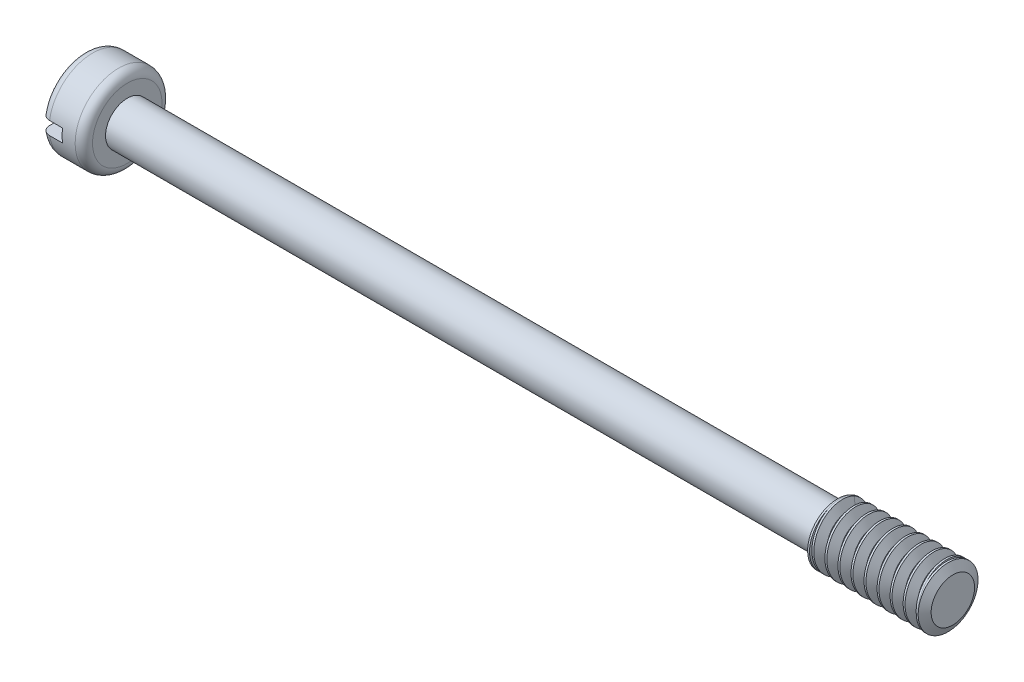
SolidWorks part; units mm, degrees
ref_plane "Front Plane" through (0, 0, 0) normal (0, 0, 1) x (1, 0, 0)
ref_plane "Top Plane" through (0, 0, 0) normal (0, 1, 0) x (1, 0, 0)
ref_plane "Right Plane" through (0, 0, 0) normal (1, 0, 0) x (0, 0, -1)
sketch "Sketch1" plane through (0, 0, 0) normal (0, 0, 1) x (1, 0, 0)
  line L0 (0, 0.8) -> (0, 0)
  line L1 (0, 0) -> (20, 0)
  line L2 (20, 0) -> (20, 0.5)
  line L3 (20, 0.5) -> (1, 0.5)
  line L4 (1, 0.5) -> (1, 0.8)
  line L5 (0.8, 1) -> (0.2, 1)
  arc A0 (1, 0.8) -> (0.8, 1) centre (0.8, 0.8) ccw
  arc A1 (0, 0.8) -> (0.2, 1) centre (0.2, 0.8) cw
  point P9 (1, 1)
  point P12 (0, 1)
  dimension "D5" = 0.2
  dimension "D1" = 20
  dimension "D2" = 0.5
  dimension "D3" = 1
  dimension "D4" = 1
revolve "Revolve2" add sketch "Sketch1" angle 360 about L1
thread "Thread1" pitch 0.35 method extrude profile "Thread Profile1" start angle 0, offset 0, length 2.5, pitch 0.3, diameter 1
ref_plane "Plane1" through (20, 0, 0.5) normal (0, -1, 0) x (0, 0, 1)
sketch "Thread Profile1" plane through (20, 0, 0.5) normal (0, -1, 0) x (0, 0, 1)
  line L0 (0, 0) -> (0, 0.35) construction
  line L1 (0, 0) -> (0.1894, 0.1094)
  line L2 (0.1894, 0.1094) -> (0.1894, 0.1531)
  line L3 (0.1894, 0.1531) -> (0, 0.2625)
  line L4 (0.1894, 0.1312) -> (0, 0.1312) construction
  line L11 (0, 0) -> (0, 0.2625)
  point P2 (0, 0)
  dimension "Pitch" = 0.35
  dimension "Profile_Angle" = 60
  dimension "Profile_Land" = 0.0437
  dimension "Profile_Height" = 0.1894
sketch "Sketch4" plane through (0, 0, 0) normal (0, -1, 0) x (1, 0, 0)
  line L4 (19.8906, 0.6894) -> (19.8469, 0.6894)
  line L5 (19.8469, 0.6894) -> (19.7375, 0.5)
  line L6 (19.7375, 0.5) -> (20, 0.5)
  line L7 (20, 0.5) -> (19.8906, 0.6894)
  line L8 (19.8906, 0.6894) -> (19.8469, 0.6894)
  line L9 (19.8469, 0.6894) -> (19.7375, 0.5)
  line L10 (19.7375, 0.5) -> (20, 0.5)
  line L11 (20, 0.5) -> (19.8906, 0.6894)
  dimension "D1" = 0
revolve "Revolve3" add sketch "Sketch4" angle 360 about axis through (0, 0, 0) along (-1, 0, 0)
sketch "Sketch5" plane through (0, 0, 0) normal (0, -0.5, -0.866) x (-1, 0, 0)
  line L4 (-17.3469, 0.6894) -> (-17.3906, 0.6894)
  line L5 (-17.3906, 0.6894) -> (-17.5, 0.5)
  line L6 (-17.5, 0.5) -> (-17.2375, 0.5)
  line L7 (-17.2375, 0.5) -> (-17.3469, 0.6894)
  line L8 (-17.3469, 0.6894) -> (-17.3906, 0.6894)
  line L9 (-17.3906, 0.6894) -> (-17.5, 0.5)
  line L10 (-17.5, 0.5) -> (-17.2375, 0.5)
  line L11 (-17.2375, 0.5) -> (-17.3469, 0.6894)
  dimension "D1" = 0
revolve "Revolve4" add sketch "Sketch5" angle 360 about axis through (0, 0, 0) along (-1, 0, 0)
sketch "Sketch6" plane through (0, 0, 0) normal (-1, 0, 0) x (0, 0, 1)
  line L1 (0.15, -0.7858) -> (-0.15, -0.7858)
  line L2 (0.15, -0.7858) -> (0.15, 0.7858)
  line L3 (0.15, 0.7858) -> (-0.15, 0.7858)
  line L4 (-0.15, -0.7858) -> (-0.15, 0.7858)
  line L5 (0.15, -0.7858) -> (-0.15, 0.7858) construction
  line L6 (0.15, 0.7858) -> (-0.15, -0.7858) construction
  line L7 (1, -0.15) -> (-1, -0.15)
  line L8 (1, -0.15) -> (1, 0.15)
  line L9 (1, 0.15) -> (-1, 0.15)
  line L10 (-1, -0.15) -> (-1, 0.15)
  line L11 (1, -0.15) -> (-1, 0.15) construction
  line L12 (1, 0.15) -> (-1, -0.15) construction
  circle A0 centre (0, 0) radius 0.8 construction
  circle A1 centre (0, 0) radius 1 construction
  point P0 (0, 0)
  point P6 (0, 0)
  circle M9 centre (0, 0) radius 0.8
  dimension "D1" = 0.3
extrude "Cut-Extrude2" cut sketch "Sketch6" against normal blind 0.5 contours L9 L2 L3 L4 | L9 L2 L7 M9 | L4 L9 L7 M9 | L2 L7 L4 L1 | L8 L9 L7 M9 | L10 L7 L9 M9 | L2 L9 L4 L7 region at (0, -0.4679, 0) region at (0, 0, 0) region at (0, 0, 0.4727) region at (0, 0, 0.8976) region at (0, 0, -0.4727) region at (0, 0, -0.8976) region at (0, 0.4679, 0)
